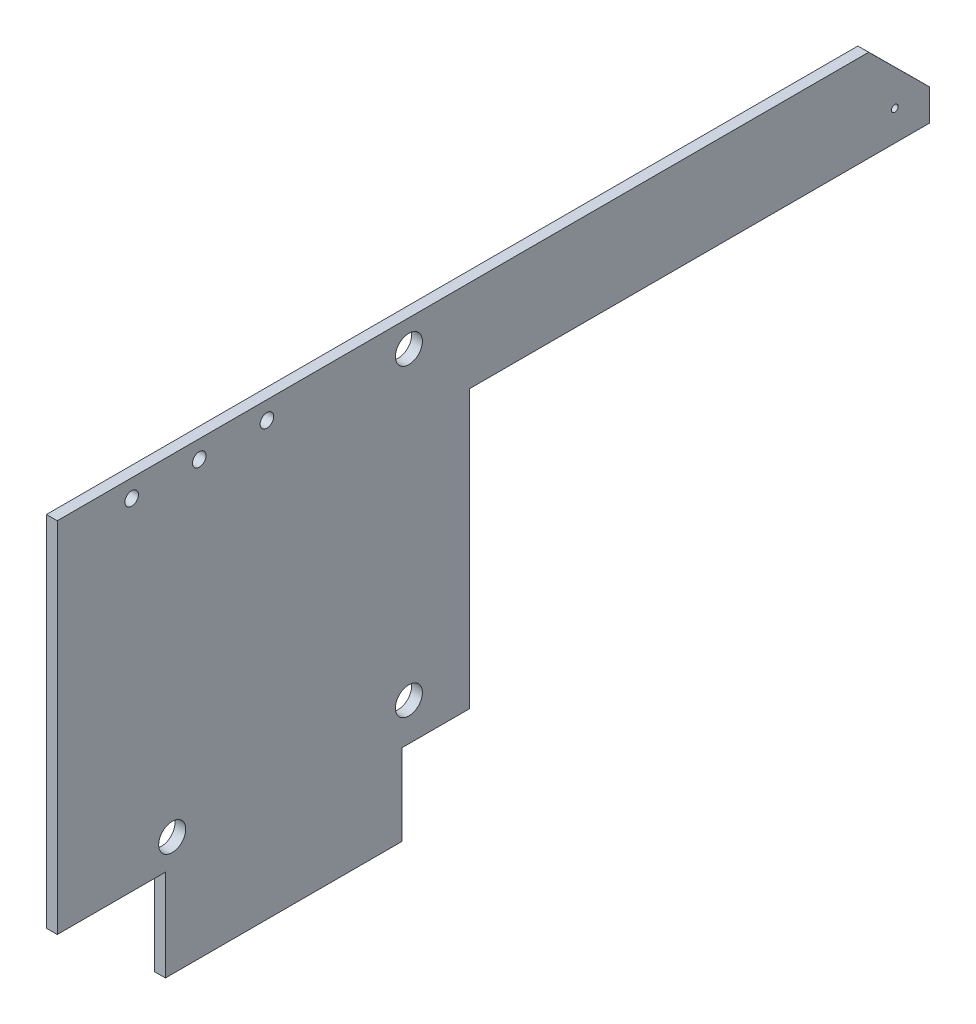
SolidWorks part; units mm, degrees
ref_plane "Front Plane" through (0, 0, 0) normal (0, 0, 1) x (1, 0, 0)
ref_plane "Top Plane" through (0, 0, 0) normal (0, 1, 0) x (1, 0, 0)
ref_plane "Right Plane" through (0, 0, 0) normal (1, 0, 0) x (0, 0, -1)
sketch "Sketch1" plane through (0, 0, 0) normal (1, 0, 0) x (0, 0, -1)
  line L0 (3, 11) -> (3, 64)
  line L1 (3, 64) -> (123, 64)
  line L2 (123, 64) -> (132, 55.0634)
  line L3 (132, 55.0634) -> (132, 50.4234)
  line L4 (132, 50.4234) -> (64, 50.4234)
  line L5 (64, 50.4234) -> (64, 9.4361)
  line L6 (64, 9.4361) -> (54, 9.4361)
  line L7 (54, 9.4361) -> (54, -2.5639)
  line L8 (54, -2.5639) -> (19, -2.5639)
  line L9 (19, -2.5639) -> (19, 11)
  line L10 (19, 11) -> (3, 11)
  line L11 (125.6318, 53.6442) -> (129.503, 57.5428) construction
  line L12 (129.503, 57.5428) -> (114.3538, 42.2861) construction
  circle A0 centre (20, 15) radius 2
  circle A1 centre (55, 15) radius 2
  circle A2 centre (55, 60) radius 2
  circle A3 centre (14, 61.35) radius 1
  circle A4 centre (24, 61.35) radius 1
  circle A5 centre (34, 61.35) radius 1
  circle A6 centre (126.8618, 54.8829) radius 0.5
  circle A7 centre (14, 61.35) radius 0.5 construction
  circle A8 centre (24, 61.35) radius 0.5 construction
  circle A9 centre (34, 61.35) radius 0.5 construction
  circle A12 centre (55, 60) radius 2 construction
  circle A13 centre (55, 15) radius 2 construction
  circle A14 centre (20, 15) radius 2 construction
  circle A15 centre (126.8618, 54.8829) radius 0.5 construction
  dimension "D1" = 2
  dimension "D2" = 120
  dimension "D3" = 16
  dimension "D4" = 10
  dimension "D5" = 35
  dimension "D6" = 68
  dimension "D7" = 53
  dimension "D8" = 13.5639
  dimension "D9" = 40.9874
  dimension "D10" = 12
  dimension "D11" = 11
  dimension "D12" = 3
extrude "Boss-Extrude1" add sketch "Sketch1" along normal blind 1.6
